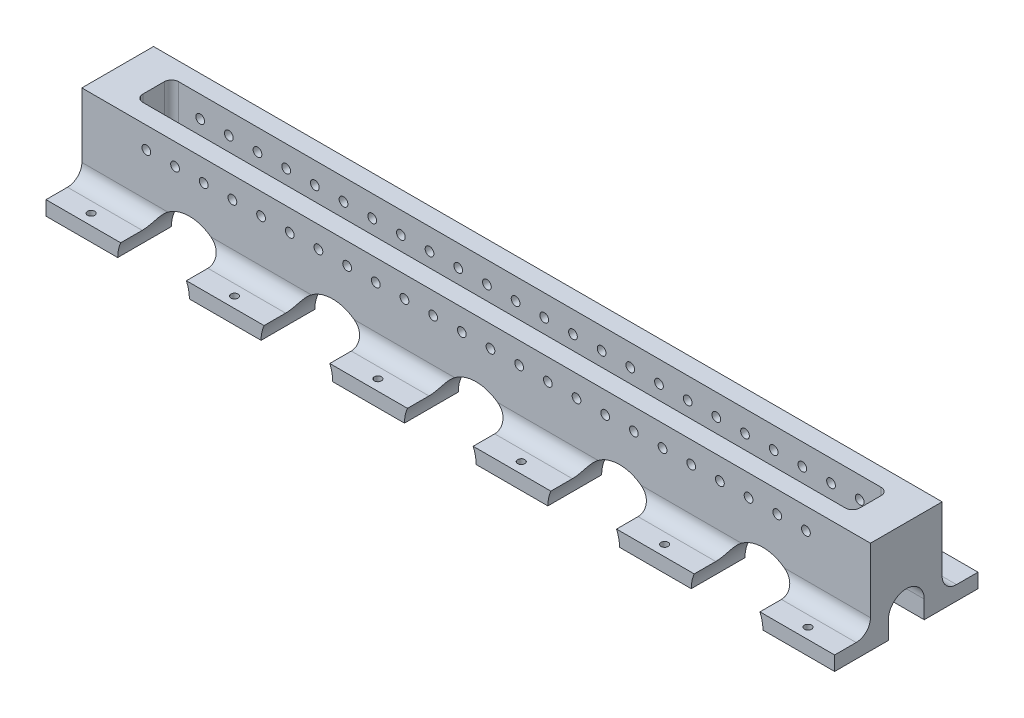
SolidWorks part; units mm, degrees
ref_plane "Front Plane" through (0, 0, 0) normal (0, 0, 1) x (1, 0, 0)
ref_plane "Top Plane" through (0, 0, 0) normal (0, 1, 0) x (1, 0, 0)
ref_plane "Right Plane" through (0, 0, 0) normal (1, 0, 0) x (0, 0, -1)
sketch "Sketch1" plane through (0, 0, 0) normal (0, 1, 0) x (1, 0, 0)
  line L1 (-50, -2.5) -> (50, -2.5)
  line L2 (-50, -2.5) -> (-50, 2.5)
  line L3 (-50, 2.5) -> (50, 2.5)
  line L4 (50, -2.5) -> (50, 2.5)
  line L5 (-50, -2.5) -> (50, 2.5) construction
  line L6 (-50, 2.5) -> (50, -2.5) construction
  line L7 (-55, -5) -> (55, -5)
  line L8 (-55, -5) -> (-55, 5)
  line L9 (-55, 5) -> (55, 5)
  line L10 (55, -5) -> (55, 5)
  line L11 (-55, -5) -> (55, 5) construction
  line L12 (-55, 5) -> (55, -5) construction
  point P0 (0, 0)
  point P6 (0, 0)
  dimension "D1" = 5
  dimension "D2" = 10
  dimension "D3" = 100
  dimension "D4" = 110
extrude "Boss-Extrude1" add sketch "Sketch1" along normal blind 13
sketch "Sketch2" plane through (55, 0, 0) normal (1, 0, 0) x (0, 0, -1)
  line L0 (0, 0) -> (0, 13) construction
  line L1 (-5, 0) -> (5, 0) construction
  line L3 (0, 0) -> (0, 13) construction
  line L4 (-5, 13) -> (5, 13) construction
  line L6 (-2.5, 0) -> (2.5, 0)
  line L7 (-2.5, 0) -> (-2.5, 5)
  line L8 (-2.5, 5) -> (2.5, 5)
  line L9 (2.5, 0) -> (2.5, 5)
  dimension "D1" = 5
  dimension "D2" = 5
extrude "Cut-Extrude1" cut sketch "Sketch2" against normal through all
fillet "Fillet1" radius 2.5 4 edges at (52.5, 5, 2.5) (52.5, 5, -2.5) (-52.5, 5, -2.5) (-52.5, 5, 2.5) tangent propagation no
sketch "Sketch3" plane through (0, 0, 5) normal (0, 0, 1) x (1, 0, 0)
  line L0 (-55, 10) -> (55, 10) construction
  line L1 (-55, 13) -> (-55, 0) construction
  line L2 (55, 13) -> (55, 0) construction
  line L3 (-55, 13) -> (55, 13) construction
  line L4 (-50, 10) -> (-50, 13) construction
  circle A0 centre (-46, 10) radius 0.61
  dimension "D2" = 1.22
  dimension "D3" = 4
  dimension "D1" = 3
extrude "Cut-Extrude2" cut sketch "Sketch3" against normal through all
pattern_linear "LPattern1" count 24 spacing 4 along (1, 0, 0) of "Cut-Extrude2"
sketch "Sketch6" plane through (0, 0, 0) normal (0, -1, 0) x (1, 0, 0)
  line L0 (-55, -5) -> (-55, -2.5) construction
  line L1 (55, -5) -> (-55, -5)
  line L2 (55, -5) -> (55, -10)
  line L3 (55, -10) -> (-55, -10)
  line L4 (-55, -5) -> (-55, -10)
  line L5 (55, 5) -> (55, 2.5) construction
  line L6 (55, 5) -> (-55, 5)
  line L7 (55, 5) -> (55, 10)
  line L8 (55, 10) -> (-55, 10)
  line L9 (-55, 5) -> (-55, 10)
  line L10 (-55, 2.5) -> (-55, 5) construction
  line L11 (-55, 5) -> (55, 5) construction
  dimension "D1" = 5
  dimension "D2" = 5
extrude "Boss-Extrude2" add sketch "Sketch6" against normal blind 2
fillet "Fillet2" radius 2 2 edges
sketch "Sketch5" plane through (0, 0, 5) normal (0, 0, 1) x (1, 0, 0)
  line L0 (-55, 0) -> (55, 0) construction
  line L1 (-50, 0) -> (-50, 13) construction
  line L2 (-55, 13) -> (55, 13) construction
  line L3 (-45, 0) -> (-35, 0)
  arc A0 (-45, 0) -> (-35, 0) centre (-40, 0) cw
  dimension "D1" = 5
  dimension "D2" = 10
extrude "Cut-Extrude4" cut sketch "Sketch5" against normal through all both and the other way through all
pattern_linear "LPattern2" count 5 spacing 20 along (1, 0, 0) of "Cut-Extrude4"
sketch "Sketch7" plane through (0, 2, 0) normal (0, 1, 0) x (1, 0, 0)
  line L0 (49.7913, 10) -> (49.7913, 8.5) construction
  line L1 (44.5826, 10) -> (55, 10) construction
  line L2 (49.7913, 8.5) -> (44.5826, 8.5) construction
  line L3 (44.5826, 7) -> (44.5826, 10) construction
  line L4 (49.7913, -10) -> (49.7913, -8.5) construction
  line L5 (55, -10) -> (44.5826, -10) construction
  line L6 (44.5826, -8.5) -> (49.7913, -8.5) construction
  line L7 (44.5826, -7) -> (44.5826, -10) construction
  circle A0 centre (49.7913, 8.5) radius 0.5
  circle A1 centre (49.7913, -8.5) radius 0.5
  dimension "D1" = 1
extrude "Cut-Extrude5" cut sketch "Sketch7" against normal blind 2
pattern_linear "LPattern3" count 24 spacing 20 along (-1, 0, 0) of "Cut-Extrude5"
fillet "Fillet3" radius 1 4 edges at (-50, 7.75, 2.5) (-50, 7.75, -2.5) (50, 7.75, -2.5) (50, 7.75, 2.5)
ref_plane "Plane1" through (30, 0, 0) normal (-1, 0, 0) x (0, 0, 1)
sketch "Sketch9" plane through (30, 0, 0) normal (-1, 0, 0) x (0, 0, 1)
  line L0 (-2.5, 5.5) -> (2.5, 5.5) construction
  line L1 (-2.5, 2.5) -> (-2.5, 13) construction
  line L2 (2.5, 5.5) -> (2.5, 3)
  line L3 (2.5, 13) -> (2.5, 2.5) construction
  line L4 (-2.5, 0) -> (2.5, 0)
  line L5 (-2.5, 5) -> (-2.5, 0)
  line L6 (2.5, 5) -> (-2.5, 5)
  line L7 (2.5, 0) -> (2.5, 5)
  line L8 (-2.5, 0) -> (2.5, 0) construction
  line L9 (-2.5, 5) -> (-2.5, 0) construction
  line L10 (2.5, 5) -> (-2.5, 5) construction
  line L11 (2.5, 0) -> (2.5, 5) construction
  line L12 (0, 0) -> (0, 15.9626) construction
  line L13 (-2.5, 5.5) -> (-2.5, 3)
  line L15 (-2.5, 5.5) -> (-2.5, 6.5)
  line L16 (-2.5, 6.5) -> (0, 6.5)
  line L17 (0, 6.5) -> (2.5, 6.5)
  line L18 (2.5, 6.5) -> (2.5, 5.5)
  arc A0 (-2.5, 3) -> (0, 5.5) centre (0, 3) cw
  arc A1 (2.5, 3) -> (0, 5.5) centre (0, 3) ccw
  dimension "D2" = 1
  dimension "D3" = 2.5
  dimension "D4" = 3
  dimension "D1" = 0
extrude "Boss-Extrude3" add sketch "Sketch9" along normal blind 1 and the other way blind 1
pattern_linear "LPattern4" count 4 spacing 20 along (-1, 0, 0) of "Boss-Extrude3"
